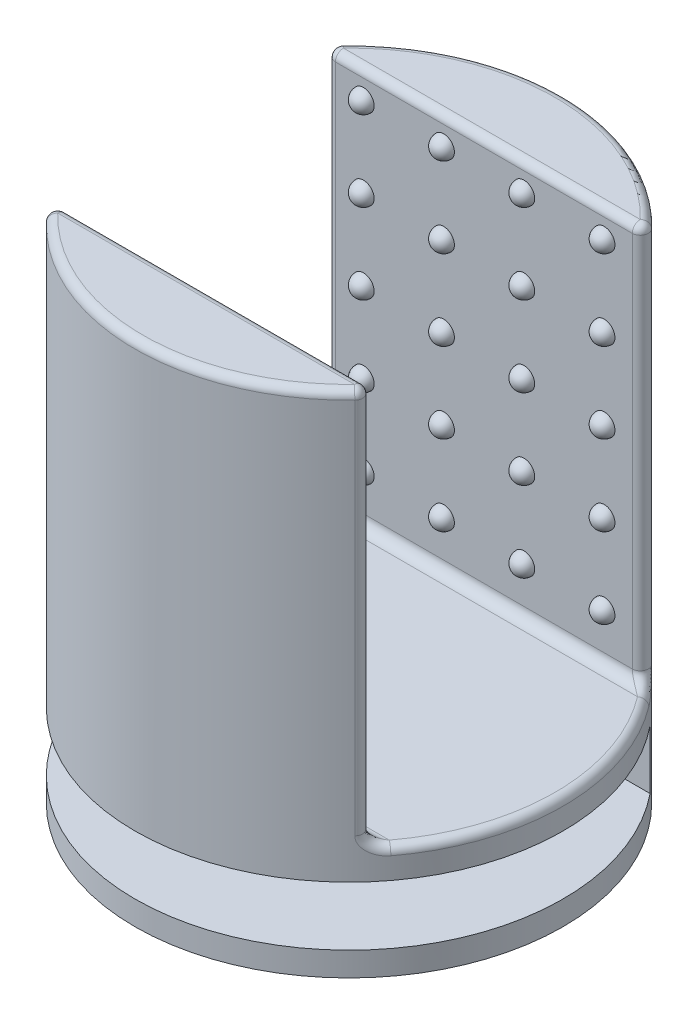
SolidWorks part; units mm, degrees
ref_plane "Front Plane" through (0, 0, 0) normal (0, 0, 1) x (1, 0, 0)
ref_plane "Top Plane" through (0, 0, 0) normal (0, 1, 0) x (1, 0, 0)
ref_plane "Right Plane" through (0, 0, 0) normal (1, 0, 0) x (0, 0, -1)
ref_plane "Plane1" through (-3.75, 0, 0) normal (1, 0, 0) x (0, 0, -1)
sketch "Sketch2" plane through (0, 0, 0) normal (0, 1, 0) x (1, 0, 0)
  line L1 (-35, 12.5) -> (35, 12.5)
  line L2 (-35, 12.5) -> (-35, -12.5)
  line L3 (-35, -12.5) -> (35, -12.5)
  line L4 (35, 12.5) -> (35, -12.5)
  line L5 (-35, 12.5) -> (35, -12.5) construction
  line L6 (-35, -12.5) -> (35, 12.5) construction
  point P0 (0, 0)
  dimension "D1" = 25
  dimension "D2" = 70
sketch "Sketch3" plane through (0, 0, 0) normal (0, 1, 0) x (1, 0, 0)
  circle A0 centre (0, 0) radius 20
  dimension "D1" = 40
extrude "Boss-Extrude1" add sketch "Sketch3" along normal blind 40
sketch "Sketch4" plane through (0, 40, 0) normal (0, 1, 0) x (1, 0, 0)
  line L8 (-35.1, 12.6) -> (-35.1, -12.6)
  line L9 (35.1, 12.6) -> (-35.1, 12.6)
  line L10 (35.1, -12.6) -> (35.1, 12.6)
  line L11 (-35.1, -12.6) -> (35.1, -12.6)
  line L12 (-35.1, 12.6) -> (-35.1, -12.6)
  line L13 (35.1, 12.6) -> (-35.1, 12.6)
  line L14 (35.1, -12.6) -> (35.1, 12.6)
  line L15 (-35.1, -12.6) -> (35.1, -12.6)
  dimension "D1" = 0.1
extrude "Cut-Extrude1" cut sketch "Sketch4" against normal offset from surface (37 mm away) 3 up to face at (0, 0, 20)
sketch "Sketch5" plane through (-3.75, 0, 0) normal (1, 0, 0) x (0, 0, -1)
  line L0 (-12.6, 40) -> (-12.6, 3) construction
  line L1 (-12.6, 40) -> (-12.6, 3) construction
  line L2 (-11.6, 37.5) -> (-13.6, 37.5) construction
  line L3 (-11.6, 37.5) -> (-13.6, 37.5)
  arc A0 (-11.6, 37.5) -> (-13.6, 37.5) centre (-12.6, 37.5) ccw
  point P4 (-12.6, 37.5)
  dimension "D1" = 2.5
  dimension "D2" = 2
revolve "Revolve1" add sketch "Sketch5" angle 360 about L3
pattern_linear "LPattern1" count 3 spacing 7.5 along (1, 0, 0) count 2 spacing 7.5 along (-1, 0, 0) of "Revolve1" pattern seed only yes
pattern_linear "LPattern2" count 5 spacing 7.5 along (0, -1, 0) of "LPattern1"
mirror "Mirror1" about plane through (0, 0, 0) normal (0, 0, 1) of "LPattern2", "LPattern1"
fillet "Fillet3" radius 1 2 edges at (0, 3, 12.6) (0, 3, -12.6)
fillet "Fillet4" radius 0.75 10 edges at (15.6511, 3.4759, -12.4517) (20, 3, 0) (15.7314, 3.3386, 12.35) (-15.7314, 3.3386, -12.35) (-20, 3, 0) (-15.6511, 3.4759, 12.4517) (15.5319, 22, -12.6) (-15.5319, 22, -12.6) (15.5319, 22, 12.6) (-15.5319, 22, 12.6)
fillet "Fillet5" radius 0.75 8 edges at (-14.5588, 40, 13.0564) (0, 40, 12.6) (14.5588, 40, 13.0564) (0, 40, 20) (-14.5588, 40, -13.0564) (0, 40, -20) (14.5588, 40, -13.0564) (0, 40, -12.6)
sketch "Sketch6" plane through (0, 0, 0) normal (0, -1, 0) x (1, 0, 0)
  circle A1 centre (0, 0) radius 20
  circle A2 centre (0, 0) radius 20
  dimension "D1" = 0
extrude "Boss-Extrude2" add sketch "Sketch6" along normal blind 7.5
sketch "Sketch7" plane through (0, 0, 0) normal (0, 0, 1) x (1, 0, 0)
  line L1 (-20, -5.25) -> (20, -5.25)
  line L2 (-20, -5.25) -> (-20, 0.25)
  line L3 (-20, 0.25) -> (20, 0.25)
  line L4 (20, -5.25) -> (20, 0.25)
  line L5 (-20, -5.25) -> (20, 0.25) construction
  line L6 (-20, 0.25) -> (20, -5.25) construction
  line L11 (-15.9609, 2.25) -> (-20, 2.25) construction
  point P0 (0, -2.5)
  point P5 (0, -6.5072)
  point P15 (0, 1.5)
  dimension "D1" = 5.5
  dimension "D2" = 2
  dimension "D3" = 40
extrude "Cut-Extrude2" cut sketch "Sketch7" against normal up to vertex (-12.6 mm away) and the other way through all up to point (-13.8687, 4, 12.6)
sketch "Sketch8" plane through (0, -7.5, 0) normal (0, -1, 0) x (1, 0, 0)
  line L1 (9.75, 15) -> (-9.75, 15)
  line L2 (9.75, 15) -> (9.75, -15)
  line L3 (9.75, -15) -> (-9.75, -15)
  line L4 (-9.75, 15) -> (-9.75, -15)
  line L5 (9.75, 15) -> (-9.75, -15) construction
  line L6 (9.75, -15) -> (-9.75, 15) construction
  point P0 (0, 0)
  dimension "D1" = 19.5
  dimension "D2" = 30
extrude "Cut-Extrude3" cut sketch "Sketch8" against normal blind 0.75
